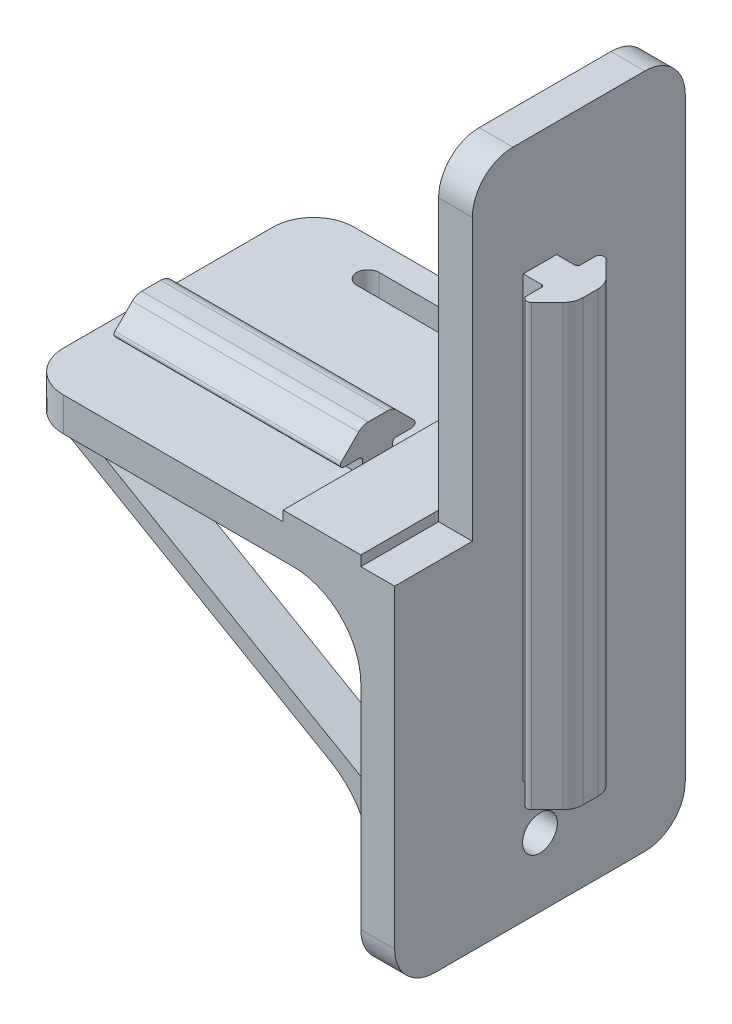
SolidWorks part; units mm, degrees
ref_plane "Front Plane" through (0, 0, 0) normal (0, 0, 1) x (1, 0, 0)
ref_plane "Top Plane" through (0, 0, 0) normal (0, 1, 0) x (1, 0, 0)
ref_plane "Right Plane" through (0, 0, 0) normal (1, 0, 0) x (0, 0, -1)
ref_plane "Plane3" through (0, 275, 0) normal (0, 1, 0) x (1, 0, 0)
sketch "Sketch1" plane through (0, 275, 0) normal (0, 1, 0) x (1, 0, 0)
  line L0 (389.6298, -111.5897) -> (387.1298, -111.5897)
  line L1 (389.6298, -106.6597) -> (387.1298, -106.6597)
  line L2 (387.1298, -106.6597) -> (387.1298, -111.5897)
  line L7 (390.3298, -111.6997) -> (389.6298, -111.6997) construction
  line L8 (389.6298, -106.5497) -> (390.3298, -106.5497) construction
  line L9 (390.6298, -114.1689) -> (390.6298, -111.9997) construction
  line L10 (394.3011, -112.3806) -> (391.9613, -114.7204) construction
  line L11 (395.1798, -107.9902) -> (395.1798, -110.2593) construction
  line L12 (390.6298, -106.2497) -> (390.6298, -104.0806) construction
  line L13 (391.9613, -103.5291) -> (394.3011, -105.8689) construction
  line L14 (389.6298, -106.6597) -> (390.3298, -106.6597)
  line L15 (390.7398, -106.2497) -> (390.7398, -104.0806)
  line L16 (391.8836, -103.6069) -> (394.2233, -105.9466)
  line L17 (395.0698, -107.9902) -> (395.0698, -110.2593)
  line L18 (394.2233, -112.3028) -> (391.8836, -114.6426)
  line L19 (390.7398, -114.1689) -> (390.7398, -111.9997)
  line L20 (390.3298, -111.5897) -> (389.6298, -111.5897)
  arc A6 (390.6298, -111.9997) -> (390.3298, -111.6997) centre (390.3298, -111.9997) ccw construction
  arc A7 (390.3298, -106.5497) -> (390.6298, -106.2497) centre (390.3298, -106.2497) ccw construction
  arc A8 (390.6298, -114.1689) -> (391.9613, -114.7204) centre (391.4098, -114.1689) ccw construction
  arc A9 (394.3011, -112.3806) -> (395.1798, -110.2593) centre (392.1798, -110.2593) ccw construction
  arc A10 (395.1798, -107.9902) -> (394.3011, -105.8689) centre (392.1798, -107.9902) ccw construction
  arc A11 (391.9613, -103.5291) -> (390.6298, -104.0806) centre (391.4098, -104.0806) ccw construction
  arc A12 (390.3298, -106.6597) -> (390.7398, -106.2497) centre (390.3298, -106.2497) ccw
  arc A13 (391.8836, -103.6069) -> (390.7398, -104.0806) centre (391.4098, -104.0806) ccw
  arc A14 (395.0698, -107.9902) -> (394.2233, -105.9466) centre (392.1798, -107.9902) ccw
  arc A15 (394.2233, -112.3028) -> (395.0698, -110.2593) centre (392.1798, -110.2593) ccw
  arc A16 (390.7398, -114.1689) -> (391.8836, -114.6426) centre (391.4098, -114.1689) ccw
  arc A17 (390.7398, -111.9997) -> (390.3298, -111.5897) centre (390.3298, -111.9997) ccw
  dimension "D2" = 2.5
  dimension "D1" = 0.11
ref_plane "Plane6" through (0, 245, 0) normal (0, 1, 0) x (1, 0, 0)
sketch "Sketch9" plane through (0, 245, 0) normal (0, 1, 0) x (1, 0, 0)
  line L0 (389.6298, -111.5997) -> (387.6298, -111.5997)
  line L1 (387.6298, -106.6497) -> (387.6298, -111.5997)
  line L7 (390.3298, -111.6897) -> (389.6298, -111.6897) construction
  line L8 (390.6298, -114.1589) -> (390.6298, -111.9897) construction
  line L9 (394.3011, -112.3706) -> (391.9613, -114.7104) construction
  line L10 (395.1798, -108.0002) -> (395.1798, -110.2493) construction
  line L11 (391.9613, -103.5391) -> (394.3011, -105.8789) construction
  line L12 (389.6298, -106.5597) -> (390.3298, -106.5597) construction
  line L13 (390.6298, -106.2597) -> (390.6298, -104.0906) construction
  line L14 (389.6298, -106.6497) -> (390.3298, -106.6497)
  line L15 (390.7198, -106.2597) -> (390.7198, -104.0906)
  line L16 (391.8977, -103.6027) -> (394.2375, -105.9425)
  line L17 (395.0898, -108.0002) -> (395.0898, -110.2493)
  line L18 (394.2375, -112.307) -> (391.8977, -114.6468)
  line L19 (390.7198, -114.1589) -> (390.7198, -111.9897)
  line L20 (390.3298, -111.5997) -> (389.6298, -111.5997)
  line L21 (389.6298, -106.6497) -> (387.6298, -106.6497)
  arc A6 (390.6298, -111.9897) -> (390.3298, -111.6897) centre (390.3298, -111.9897) ccw construction
  arc A7 (390.6298, -114.1589) -> (391.9613, -114.7104) centre (391.4098, -114.1589) ccw construction
  arc A8 (394.3011, -112.3706) -> (395.1798, -110.2493) centre (392.1798, -110.2493) ccw construction
  arc A9 (395.1798, -108.0002) -> (394.3011, -105.8789) centre (392.1798, -108.0002) ccw construction
  arc A10 (391.9613, -103.5391) -> (390.6298, -104.0906) centre (391.4098, -104.0906) ccw construction
  arc A11 (390.3298, -106.5597) -> (390.6298, -106.2597) centre (390.3298, -106.2597) ccw construction
  arc A12 (390.3298, -106.6497) -> (390.7198, -106.2597) centre (390.3298, -106.2597) ccw
  arc A13 (391.8977, -103.6027) -> (390.7198, -104.0906) centre (391.4098, -104.0906) ccw
  arc A14 (395.0898, -108.0002) -> (394.2375, -105.9425) centre (392.1798, -108.0002) ccw
  arc A15 (394.2375, -112.307) -> (395.0898, -110.2493) centre (392.1798, -110.2493) ccw
  arc A16 (390.7198, -114.1589) -> (391.8977, -114.6468) centre (391.4098, -114.1589) ccw
  arc A17 (390.7198, -111.9897) -> (390.3298, -111.5997) centre (390.3298, -111.9897) ccw
  dimension "D2" = 2
  dimension "D3" = 2
  dimension "D1" = 0.09
extrude "Boss-Extrude5" add sketch "Sketch9" against normal blind 50
ref_plane "Plane8" through (387.6298, 0, 0) normal (-1, 0, 0) x (0, 0, 1)
sketch "Sketch11" plane through (387.6298, 0, 0) normal (-1, 0, 0) x (0, 0, 1)
  line L1 (87.6247, 270) -> (130.6247, 270)
  line L2 (87.6247, 270) -> (87.6247, 170)
  line L3 (87.6247, 170) -> (130.6247, 170)
  line L4 (130.6247, 270) -> (130.6247, 170)
  line L5 (109.1247, 245) -> (109.1247, 188.6769) construction
  line L6 (106.6497, 245) -> (111.5997, 245) construction
  line L7 (106.6497, 220) -> (141.9101, 220) construction
  line L8 (106.6497, 195) -> (106.6497, 245) construction
  dimension "D1" = 21.5
  dimension "D2" = 21.5
  dimension "D3" = 50
  dimension "D4" = 50
extrude "Boss-Extrude6" add sketch "Sketch11" along normal blind 5
sketch "Sketch12" plane through (387.6298, 0, 0) normal (-1, 0, 0) x (0, 0, 1)
  line L0 (130.6247, 220) -> (87.6247, 220) construction
  line L1 (130.6247, 170) -> (130.6247, 270) construction
  line L2 (87.6247, 270) -> (87.6247, 170) construction
  line L3 (130.6247, 170) -> (130.6247, 270) construction
  line L4 (130.6247, 222.5) -> (89.1247, 222.5)
  line L5 (130.6247, 222.5) -> (130.6247, 217.5)
  line L6 (130.6247, 217.5) -> (89.1247, 217.5)
  line L7 (89.1247, 222.5) -> (87.6247, 222.5)
  line L8 (89.1247, 217.5) -> (87.6247, 217.5)
  line L9 (87.6247, 222.5) -> (87.6247, 217.5)
  dimension "D1" = 2.5
  dimension "D2" = 2.5
extrude "Boss-Extrude8" add sketch "Sketch12" along normal blind 55
sketch "Sketch13" plane through (387.6298, 0, 0) normal (-1, 0, 0) x (0, 0, 1)
  line L0 (119.1247, 8.5) -> (119.1247, 408.5) construction
  line L1 (119.1247, 222.5) -> (119.1247, 270)
  line L2 (87.6247, 222.5) -> (130.6247, 222.5) construction
  line L3 (119.1247, 222.5) -> (130.6247, 222.5)
  line L4 (130.6247, 222.5) -> (130.6247, 270) construction
  line L5 (130.6247, 270) -> (87.6247, 270) construction
  line L6 (130.6247, 222.5) -> (130.6247, 270)
  line L7 (130.6247, 270) -> (119.1247, 270)
extrude "Cut-Extrude1" cut sketch "Sketch13" along normal blind 55
ref_plane "Plane9" through (0, 0, 129.1247) normal (0, 0, 1) x (1, 0, 0)
sketch "Sketch15" plane through (0, 0, 129.1247) normal (0, 0, 1) x (1, 0, 0)
  line L0 (335.6298, 217.5) -> (382.6298, 190.3645)
  line L1 (332.6298, 217.5) -> (382.6298, 217.5) construction
  line L2 (382.6298, 170) -> (382.6298, 217.5) construction
  line L3 (332.6298, 217.5) -> (382.6298, 217.5) construction
  line L4 (335.6298, 217.5) -> (340.6298, 217.5)
  line L7 (382.6298, 190.3645) -> (382.6298, 193.2513)
  line L8 (340.6298, 217.5) -> (382.6298, 193.2513)
  point P6 (332.6298, 217.5)
  dimension "D1" = 3
  dimension "D2" = 30
  dimension "D3" = 5
  dimension "D4" = 30
ref_plane "Plane10" through (332.6298, 0, 0) normal (-1, 0, 0) x (0, 0, 1)
ref_plane "Plane11" through (382.6298, 0, 0) normal (-1, 0, 0) x (0, 0, 1)
extrude "Boss-Extrude9" add sketch "Sketch15" against normal blind 6
fillet "Fillet7" radius 12 2 edges at (335.6298, 217.5, 126.1247) (382.6298, 190.3645, 126.1247)
ref_plane "Plane12" through (0, 0, 110.6247) normal (0, 0, 1) x (1, 0, 0)
mirror "Mirror1" about plane through (0, 0, 110.6247) normal (0, 0, 1) of "Boss-Extrude9", "Fillet7"
fillet "Fillet8" radius 6 6 edges at (385.1298, 170, 87.6247) (385.1298, 170, 130.6247) (332.6298, 220, 130.6247) (385.1298, 270, 87.6247) (385.1298, 270, 119.1247) (332.6298, 220, 87.6247)
extrude "Boss-Extrude10" add sketch "Sketch9<2>" along normal blind 8
sketch "Sketch9<2>" plane through (0, 245, 0) normal (0, 1, 0) x (1, 0, 0) same geometry as "Sketch9"
fillet "Fillet12" radius 10 1 edges at (382.6298, 217.5, 109.1247)
extrude "Boss-Extrude11" add sketch "Sketch9<3>" against normal blind 57
sketch "Sketch9<3>" plane through (0, 245, 0) normal (0, 1, 0) x (1, 0, 0) same geometry as "Sketch9"
ref_plane "Plane13" through (382.6298, 0, 0) normal (-1, 0, 0) x (0, 0, 1)
sketch "Sketch16" plane through (382.6298, 0, 0) normal (-1, 0, 0) x (0, 0, 1)
  line L1 (111.6997, 8.5) -> (111.6997, 408.5) construction
  line L3 (111.6997, 8.5) -> (111.6997, 408.5) construction
  line L4 (111.6997, 8.5) -> (111.6997, 408.5) construction
  line L5 (111.6997, 8.5) -> (111.6997, 408.5) construction
  line L6 (106.5497, 8.5) -> (106.5497, 408.5) construction
  line L7 (106.5497, 8.5) -> (106.5497, 408.5) construction
  line L9 (109.1247, 162.2841) -> (109.1247, 197.982) construction
  circle A0 centre (109.1247, 180.1331) radius 2.575
  dimension "D2" = 5.15
extrude "Cut-Extrude2" cut sketch "Sketch16" against normal blind 10
sketch "Sketch17" plane through (371.1298, 0, 0) normal (1, 0, 0) x (0, 0, -1)
  line L2 (-103.1446, 222.5) -> (-103.1446, 224)
  line L3 (-130.6247, 222.5) -> (-103.1446, 222.5)
  line L4 (-130.6247, 224) -> (-130.6247, 222.5)
  line L5 (-130.6247, 224) -> (-103.1446, 224)
  dimension "D1" = 1.5
extrude "Boss-Extrude12" add sketch "Sketch17" along normal up to surface (11.5 mm away) up to face at (382.6298, 252.5809, 103.3747)
sketch "Sketch18" [suppressed] plane through (382.6298, 0, 0) normal (1, 0, 0) x (0, 0, -1)
  line L0 (-119.1247, 222.5) -> (-119.1247, 224) construction
  line L1 (-130.6247, 224) -> (-119.1247, 224) construction
  line L2 (-119.1247, 222.5) -> (-130.6247, 222.5) construction
  line L3 (-130.6247, 222.5) -> (-130.6247, 224) construction
  line L4 (-119.1247, 222.5) -> (-119.1247, 224)
  line L5 (-130.6247, 224) -> (-119.1247, 224)
  line L6 (-119.1247, 222.5) -> (-130.6247, 222.5)
  line L7 (-130.6247, 222.5) -> (-130.6247, 224)
extrude "Boss-Extrude13" [suppressed] add sketch "Sketch18" along normal up to surface (5 mm away)
sketch "Sketch19" plane through (332.6298, 0, 0) normal (-1, 0, 0) x (0, 0, 1)
  line L12 (125.1447, 227.49) -> (125.1447, 228.51)
  line L13 (122.6447, 227.49) -> (125.1447, 227.49)
  line L14 (122.6447, 227.0027) -> (122.6447, 227.49)
  line L15 (124.745, 223.3679) -> (122.6447, 227.0027)
  line L16 (124.745, 222.5) -> (124.745, 223.3679)
  line L17 (108.5243, 222.5) -> (124.745, 222.5)
  line L18 (108.5243, 223.3679) -> (108.5243, 222.5)
  line L19 (110.6247, 227.0027) -> (108.5243, 223.3679)
  line L20 (110.6247, 227.49) -> (110.6247, 227.0027)
  line L21 (108.1247, 227.49) -> (110.6247, 227.49)
  line L22 (108.1247, 228.51) -> (108.1247, 227.49)
  line L23 (125.1447, 228.51) -> (108.1247, 228.51)
extrude "Boss-Extrude14" [suppressed] add sketch "Sketch19" against normal up to surface (33.5 mm away) from offset 5 offset against normal yes
sketch "Sketch22" plane through (332.6298, 0, 0) normal (-1, 0, 0) x (0, 0, 1)
  line L9 (114.4062, 222.5) -> (114.4062, 224.5)
  line L10 (124.6247, 222.5) -> (93.6247, 222.5) construction
  line L11 (116.6347, 229) -> (116.6347, 219.5991) construction
  line L12 (118.8632, 222.5) -> (114.4062, 222.5)
  line L13 (113.9062, 225) -> (111.6133, 225)
  line L14 (111.2597, 225.8536) -> (113.8204, 228.4142)
  line L15 (115.2346, 229) -> (116.6347, 229)
  line L16 (118.8632, 222.5) -> (118.8632, 224.5)
  line L17 (119.3632, 225) -> (121.6561, 225)
  line L18 (118.0348, 229) -> (116.6347, 229)
  line L19 (122.0096, 225.8536) -> (119.449, 228.4142)
  arc A6 (115.2346, 229) -> (113.8204, 228.4142) centre (115.2346, 227) ccw
  arc A7 (111.6133, 225) -> (111.2597, 225.8536) centre (111.6133, 225.5) cw
  arc A8 (114.4062, 224.5) -> (113.9062, 225) centre (113.9062, 224.5) ccw
  arc A9 (118.8632, 224.5) -> (119.3632, 225) centre (119.3632, 224.5) cw
  arc A10 (121.6561, 225) -> (122.0096, 225.8536) centre (121.6561, 225.5) ccw
  arc A11 (118.0348, 229) -> (119.449, 228.4142) centre (118.0348, 227) cw
  point P36 (110.4062, 225)
  point P39 (114.4062, 225)
  point P40 (115.9346, 229)
  point P48 (117.3347, 229)
  dimension "D3" = 2
  dimension "D4" = 0.5
  dimension "D7" = 0.5
  dimension "D1" = 2.5
  dimension "D2" = 4
  dimension "D5" = 45
  dimension "D6" = 6.5
extrude "Boss-Extrude15" add sketch "Sketch22" against normal blind 33.5 from offset 5 offset against normal yes
sketch "Sketch23" plane through (0, 222.5, 0) normal (0, 1, 0) x (1, 0, 0)
  line L0 (346.2798, -93.2267) -> (374.9798, -93.2267) construction
  line L1 (337.6298, -98.8287) -> (371.1298, -98.8287) construction
  line L2 (338.6298, -87.6247) -> (382.6298, -87.6247) construction
  line L3 (338.6298, -98.8287) -> (371.1298, -98.8287) construction
  line L4 (338.6298, -87.6247) -> (371.1298, -87.6247) construction
  line L6 (338.6298, -93.2267) -> (382.6298, -93.2267) construction
  line L7 (338.6298, -87.6247) -> (338.6298, -98.8287) construction
  line L10 (382.6298, -113.1247) -> (382.6298, -93.6247) construction
  line L11 (382.6298, -87.6247) -> (382.6298, -93.6247) construction
  line L12 (382.6298, -113.1247) -> (382.6298, -93.6247) construction
  line L13 (382.6298, -87.6247) -> (382.6298, -93.6247) construction
  line L14 (346.2798, -91.5767) -> (374.9798, -91.5767)
  line L15 (346.2798, -94.8767) -> (374.9798, -94.8767)
  arc A2 (346.2798, -91.5767) -> (346.2798, -94.8767) centre (346.2798, -93.2267) ccw
  arc A3 (374.9798, -94.8767) -> (374.9798, -91.5767) centre (374.9798, -93.2267) ccw
  point P10 (360.6298, -93.2267)
  point P17 (376.6298, -93.2267)
  point P18 (344.6298, -93.2267)
  dimension "D1" = 6
  dimension "3.3" = 3.3
  dimension "D2" = 6
extrude "Cut-Extrude3" cut sketch "Sketch23" against normal blind 6
